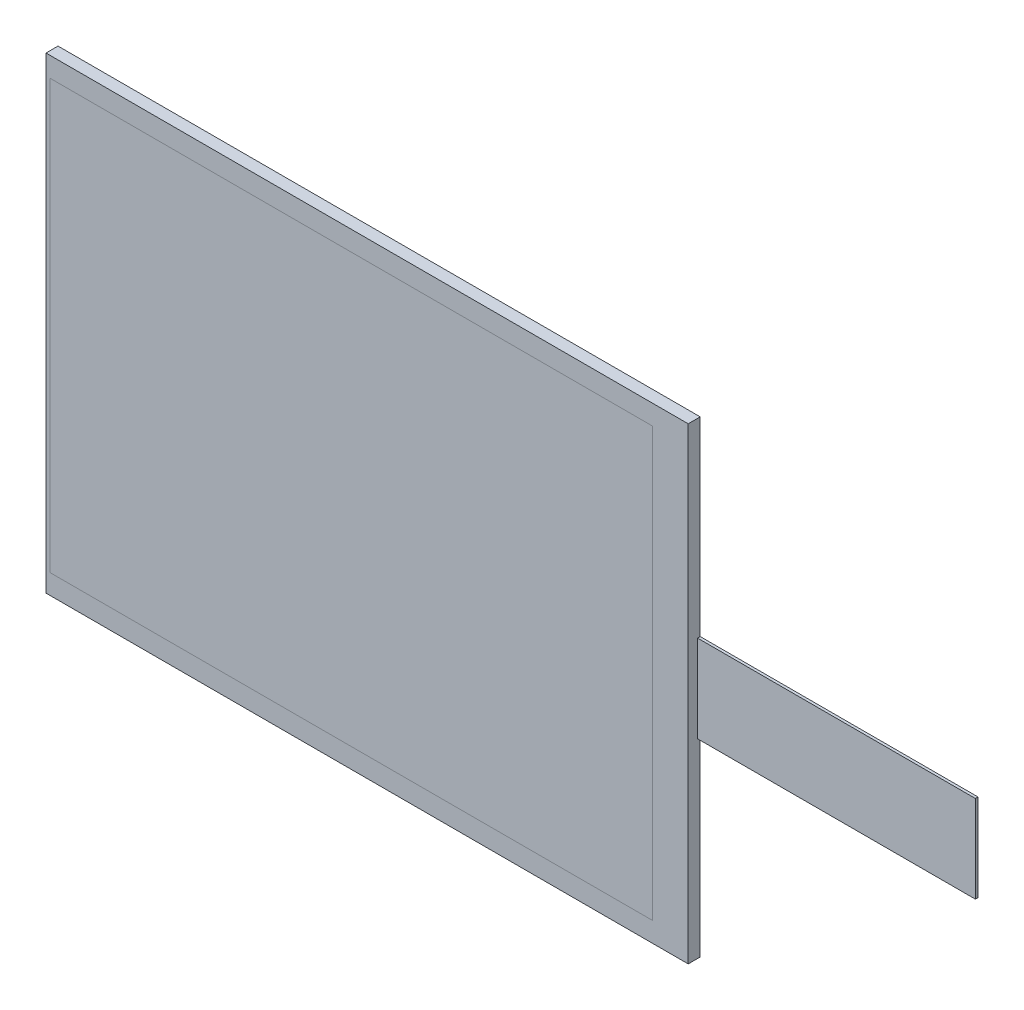
SolidWorks part; units mm, degrees
ref_plane "Front Plane" through (0, 0, 0) normal (0, 0, 1) x (1, 0, 0)
ref_plane "Top Plane" through (0, 0, 0) normal (0, 1, 0) x (1, 0, 0)
ref_plane "Right Plane" through (0, 0, 0) normal (1, 0, 0) x (0, 0, -1)
sketch "Sketch1" plane through (0, 0, 0) normal (0, 0, 1) x (1, 0, 0)
  line L1 (22.8, 16.2) -> (-22.8, 16.2)
  line L2 (22.8, 16.2) -> (22.8, -16.2)
  line L3 (22.8, -16.2) -> (-22.8, -16.2)
  line L4 (-22.8, 16.2) -> (-22.8, -16.2)
  line L5 (0, -16.2) -> (0, 16.2) construction
  line L6 (22.8, 0) -> (-22.8, 0) construction
  line L7 (25.5, 17.7) -> (-23.1, 17.7)
  line L8 (25.5, 17.7) -> (25.5, -17.7)
  line L9 (25.5, -17.7) -> (-23.1, -17.7)
  line L10 (-23.1, 17.7) -> (-23.1, -17.7)
  line L11 (1.2, -17.7) -> (1.2, 17.7) construction
  line L12 (25.5, 0) -> (-23.1, 0) construction
  line L13 (25.5, -3.3) -> (46.52, -3.3)
  line L14 (25.5, -3.3) -> (25.5, 3.3)
  line L15 (25.5, 3.3) -> (46.52, 3.3)
  line L16 (46.52, -3.3) -> (46.52, 3.3)
  line L17 (36.01, 3.3) -> (36.01, -3.3) construction
  line L18 (25.5, 0) -> (46.52, 0) construction
  point P0 (0, 0)
  point P4 (1.2, 0)
  point P8 (36.01, 0)
  dimension "D1" = 35.4
  dimension "D2" = 48.6
  dimension "D3" = 45.6
  dimension "D4" = 32.4
  dimension "D5" = 25.5
  dimension "D6" = 6.6
  dimension "D7" = 21.02
extrude "Boss-Extrude1" add sketch "Sketch1" along normal blind 0.91 contours L1 L4 L3 L2 region at (0, 0, 0)
extrude "Boss-Extrude2" add sketch "Sketch1<3>" along normal blind 0.91 separate body contours L7 L10 L9 L8 L4 L1 L2 L3 region at (24.8987, 10.5, 0)
sketch "Sketch1<3>" plane through (0, 0, 0) normal (0, 0, 1) x (1, 0, 0) same geometry as "Sketch1"
extrude "Boss-Extrude3" add sketch "Sketch1<4>" along normal blind 0.2 separate body contours L13 L16 L15 L8 region at (36.01, 0, 0)
sketch "Sketch1<4>" plane through (0, 0, 0) normal (0, 0, 1) x (1, 0, 0) same geometry as "Sketch1"
